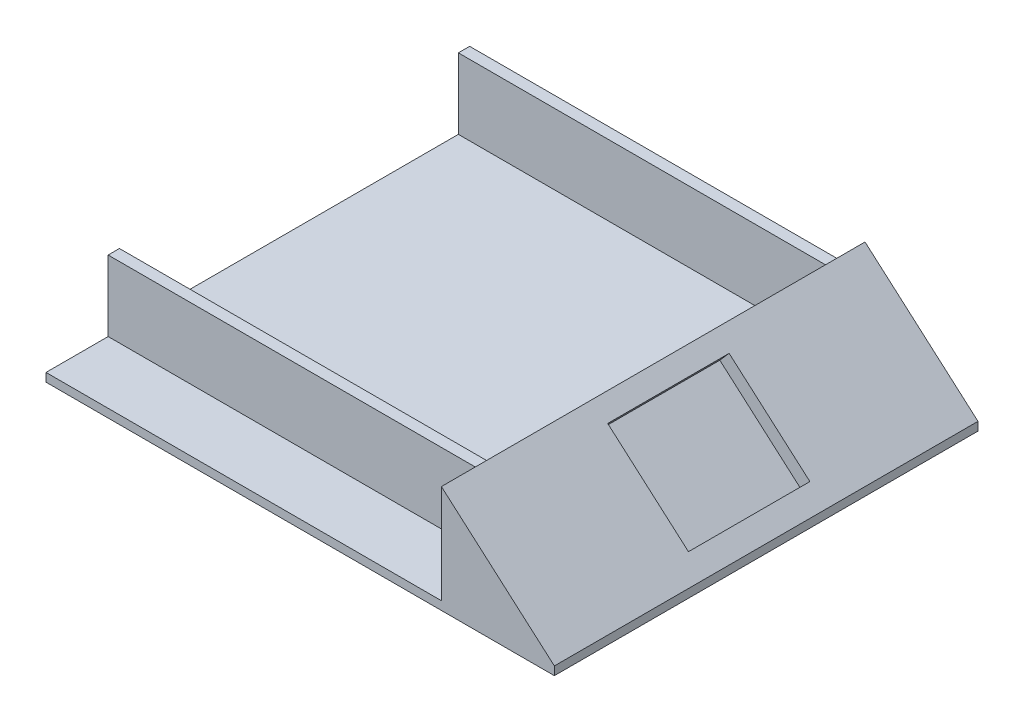
SolidWorks part; units mm, degrees
ref_plane "Front Plane" through (0, 0, 0) normal (0, 0, 1) x (1, 0, 0)
ref_plane "Top Plane" through (0, 0, 0) normal (0, 1, 0) x (1, 0, 0)
ref_plane "Right Plane" through (0, 0, 0) normal (1, 0, 0) x (0, 0, -1)
sketch "Sketch1" plane through (0, 0, 0) normal (0, 1, 0) x (1, 0, 0)
  line L1 (0, 0) -> (180, 0)
  line L2 (0, 0) -> (0, 150)
  line L3 (0, 150) -> (180, 150)
  line L4 (180, 0) -> (180, 150)
  dimension "D1" = 150
  dimension "D2" = 180
extrude "Boss-Extrude1" add sketch "Sketch1" along normal blind 3
sketch "Sketch2" plane through (0, 0, 0) normal (0, 0, 1) x (1, 0, 0)
  line L0 (180, 3) -> (140, 38)
  line L1 (140, 38) -> (140, 3)
  line L2 (0, 3) -> (180, 3) construction
  line L3 (140, 3) -> (180, 3)
  dimension "D1" = 40
  dimension "D2" = 35
extrude "Boss-Extrude2" add sketch "Sketch2" against normal blind 150
sketch "Sketch3" plane through (0, 3, 0) normal (0, 1, 0) x (1, 0, 0)
  line L0 (140, 150) -> (0, 150)
  line L1 (0, 150) -> (0, 146)
  line L2 (0, 150) -> (0, 0) construction
  line L3 (0, 146) -> (140, 146)
  line L4 (140, 150) -> (140, 0) construction
  line L5 (140, 146) -> (140, 150)
  line L7 (0, 26) -> (140, 26)
  line L8 (0, 26) -> (0, 22)
  line L9 (0, 22) -> (140, 22)
  line L10 (140, 26) -> (140, 22)
  point P16 (-20.0018, -2.2208)
  dimension "D1" = 4
  dimension "D2" = 4
  dimension "D3" = 26
extrude "Boss-Extrude3" add sketch "Sketch3" along normal blind 25
sketch "Sketch4" plane through (79.5398, 90.9027, 0) normal (0.6585, 0.7526, 0) x (0, 0, -1)
  line L1 (96.5, -87.4883) -> (53.5, -87.4883)
  line L2 (96.5, -87.4883) -> (96.5, -125.4883)
  line L3 (96.5, -125.4883) -> (53.5, -125.4883)
  line L4 (53.5, -87.4883) -> (53.5, -125.4883)
  line L5 (96.5, -87.4883) -> (53.5, -125.4883) construction
  line L6 (96.5, -125.4883) -> (53.5, -87.4883) construction
  point P0 (75, -106.4883)
  dimension "D1" = 43
  dimension "D2" = 38
  dimension "D3" = 27
  dimension "D4" = 75
extrude "Cut-Extrude1" cut sketch "Sketch4" against normal blind 5
